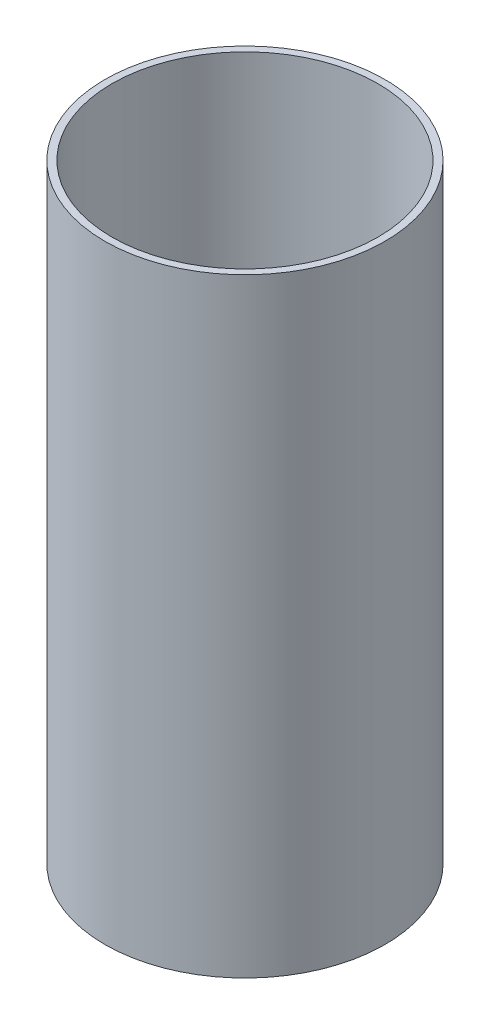
SolidWorks part; units mm, degrees
material "PVC Rigid"
ref_plane "Front Plane" through (0, 0, 0) normal (0, 0, 1) x (1, 0, 0)
ref_plane "Top Plane" through (0, 0, 0) normal (0, 1, 0) x (1, 0, 0)
ref_plane "Right Plane" through (0, 0, 0) normal (1, 0, 0) x (0, 0, -1)
sketch "Sketch1" plane through (0, 0, 0) normal (0, 1, 0) x (1, 0, 0)
  circle A0 centre (0, 0) radius 93.6625
  circle A1 centre (0, 0) radius 88.9
  dimension "D1" = 187.325
  dimension "D2" = 177.8
extrude "Boss-Extrude1" add sketch "Sketch1" along normal mid plane 407.162
ref_plane "Plane1" through (0, 0, 93.6625) normal (0, 0, 1) x (1, 0, 0)
sketch "Sketch3" plane through (0, 0, 93.6625) normal (0, 0, 1) x (1, 0, 0)
  line L0 (0, -55) -> (0, 55) construction
  line L1 (-93.6625, -203.581) -> (93.6625, -203.581) construction
  circle A0 centre (0, -197.231) radius 1.4351
  dimension "D1" = 2.8702
  dimension "D2" = 6.35
extrude "Cut-Extrude1" [suppressed] cut sketch "Sketch3" against normal blind 19.304
pattern_circular "CirPattern1" [suppressed] count 12 over 360 reverse direction yes of bodies 102
mirror "Mirror1" [suppressed] about plane through (0, 0, 0) normal (0, 1, 0)
sketch "Sketch4" [suppressed] plane through (0, 0, 93.6625) normal (0, 0, 1) x (1, 0, 0)
  line L0 (0, -103.0288) -> (0, 103.0288) construction
  circle A0 centre (0, 65.7606) radius 1.4351
  circle A1 centre (0, -65.7606) radius 1.4351
  circle A2 centre (0, 197.231) radius 1.4351 construction
  circle A3 centre (0, -197.231) radius 1.4351 construction
  dimension "D1" = 131.4704
  dimension "D2" = 131.4704
  dimension "D3" = 2.8702
  dimension "D4" = 2.8702
extrude "Cut-Extrude2" [suppressed] cut sketch "Sketch4" against normal blind 43.18
pattern_circular "CirPattern2" [suppressed] count 3 over 360 reverse direction yes of bodies 105
